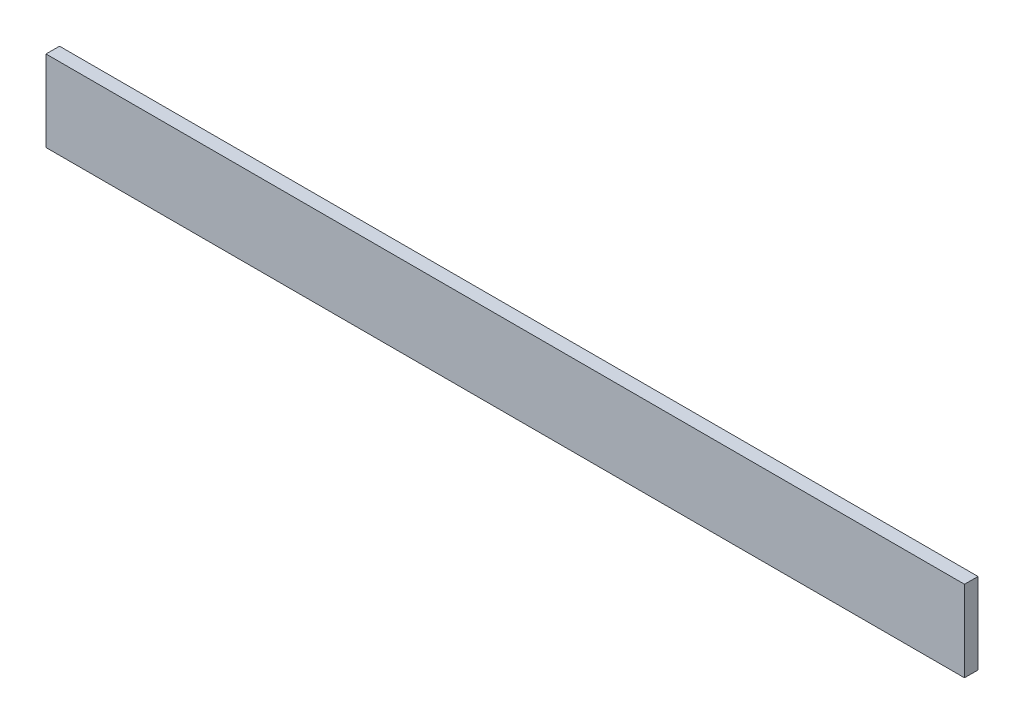
SolidWorks part; units mm, degrees
ref_plane "Front Plane" through (0, 0, 0) normal (0, 0, 1) x (1, 0, 0)
ref_plane "Top Plane" through (0, 0, 0) normal (0, 1, 0) x (1, 0, 0)
ref_plane "Right Plane" through (0, 0, 0) normal (1, 0, 0) x (0, 0, -1)
sketch "Sketch1" plane through (0, 0, 0) normal (0, 0, 1) x (1, 0, 0)
  line L1 (0, 0) -> (431.8, 0)
  line L2 (0, 0) -> (0, 38.1)
  line L3 (0, 38.1) -> (431.8, 38.1)
  line L4 (431.8, 0) -> (431.8, 38.1)
  dimension "D1" = 38.1
  dimension "D2" = 431.8
extrude "Boss-Extrude1" add sketch "Sketch1" along normal blind 6.35
